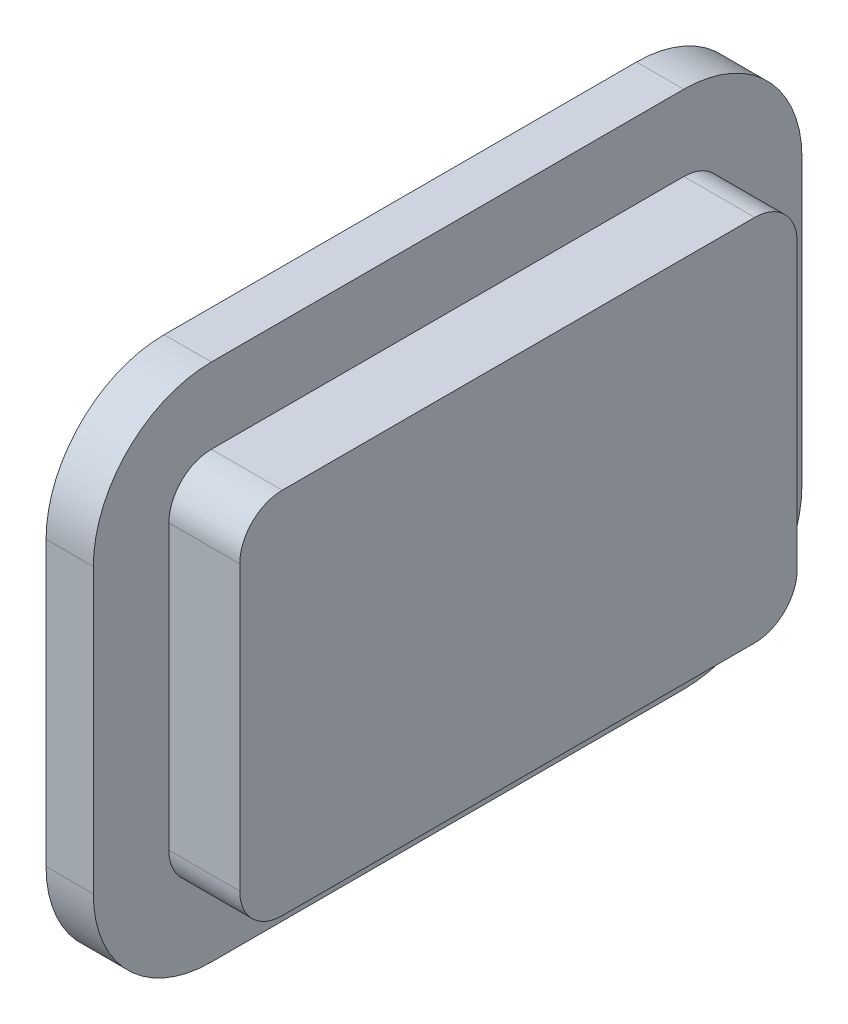
SolidWorks part; units mm, degrees
ref_plane "Front Plane" through (0, 0, 0) normal (0, 0, 1) x (1, 0, 0)
ref_plane "Top Plane" through (0, 0, 0) normal (0, 1, 0) x (1, 0, 0)
ref_plane "Right Plane" through (0, 0, 0) normal (1, 0, 0) x (0, 0, -1)
sketch "Sketch1" plane through (-60, 0, 0) normal (-1, 0, 0) x (0, 0, 1)
  line L8 (-36.3223, 9.45) -> (-26.3223, 9.45)
  line L9 (-36.3223, 9.45) -> (-26.3223, 9.45)
  line L10 (-37.2223, 16.35) -> (-37.2223, 10.35)
  line L11 (-37.2223, 16.35) -> (-37.2223, 10.35)
  line L12 (-26.3223, 17.25) -> (-36.3223, 17.25)
  line L13 (-26.3223, 17.25) -> (-36.3223, 17.25)
  line L14 (-25.4223, 10.35) -> (-25.4223, 16.35)
  line L15 (-25.4223, 10.35) -> (-25.4223, 16.35)
  line L16 (-36.3223, 7.85) -> (-26.3223, 7.85)
  line L17 (-36.3223, 7.85) -> (-26.3223, 7.85)
  line L18 (-38.8223, 16.35) -> (-38.8223, 10.35)
  line L19 (-38.8223, 16.35) -> (-38.8223, 10.35)
  line L20 (-26.3223, 18.85) -> (-36.3223, 18.85)
  line L21 (-26.3223, 18.85) -> (-36.3223, 18.85)
  line L22 (-23.8223, 10.35) -> (-23.8223, 16.35)
  line L23 (-23.8223, 10.35) -> (-23.8223, 16.35)
  arc A8 (-26.3223, 9.45) -> (-25.4223, 10.35) centre (-26.3223, 10.35) ccw
  arc A11 (-26.3223, 7.85) -> (-23.8223, 10.35) centre (-26.3223, 10.35) ccw
  arc A17 (-26.3223, 9.45) -> (-25.4223, 10.35) centre (-26.3223, 10.35) ccw
  arc A18 (-37.2223, 10.35) -> (-36.3223, 9.45) centre (-36.3223, 10.35) ccw
  arc A19 (-37.2223, 10.35) -> (-36.3223, 9.45) centre (-36.3223, 10.35) ccw
  arc A21 (-36.3223, 17.25) -> (-37.2223, 16.35) centre (-36.3223, 16.35) ccw
  arc A22 (-36.3223, 17.25) -> (-37.2223, 16.35) centre (-36.3223, 16.35) ccw
  arc A23 (-25.4223, 16.35) -> (-26.3223, 17.25) centre (-26.3223, 16.35) ccw
  arc A24 (-25.4223, 16.35) -> (-26.3223, 17.25) centre (-26.3223, 16.35) ccw
  arc A25 (-26.3223, 7.85) -> (-23.8223, 10.35) centre (-26.3223, 10.35) ccw
  arc A26 (-38.8223, 10.35) -> (-36.3223, 7.85) centre (-36.3223, 10.35) ccw
  arc A27 (-38.8223, 10.35) -> (-36.3223, 7.85) centre (-36.3223, 10.35) ccw
  arc A28 (-36.3223, 18.85) -> (-38.8223, 16.35) centre (-36.3223, 16.35) ccw
  arc A29 (-36.3223, 18.85) -> (-38.8223, 16.35) centre (-36.3223, 16.35) ccw
  arc A30 (-23.8223, 16.35) -> (-26.3223, 18.85) centre (-26.3223, 16.35) ccw
  arc A31 (-23.8223, 16.35) -> (-26.3223, 18.85) centre (-26.3223, 16.35) ccw
  dimension "D1" = 0.1
  dimension "D2" = 1.5
extrude "Boss-Extrude1" add sketch "Sketch1" along normal blind 1 contours A29 L19 A27 L17 A25 L23 A31 L21
extrude "Boss-Extrude2" add sketch "Sketch1<3>" against normal blind 1.5 contours L13 A22 L11 A19 L9 A17 L15 A24
sketch "Sketch1<3>" plane through (-60, 0, 0) normal (-1, 0, 0) x (0, 0, 1) same geometry as "Sketch1"
